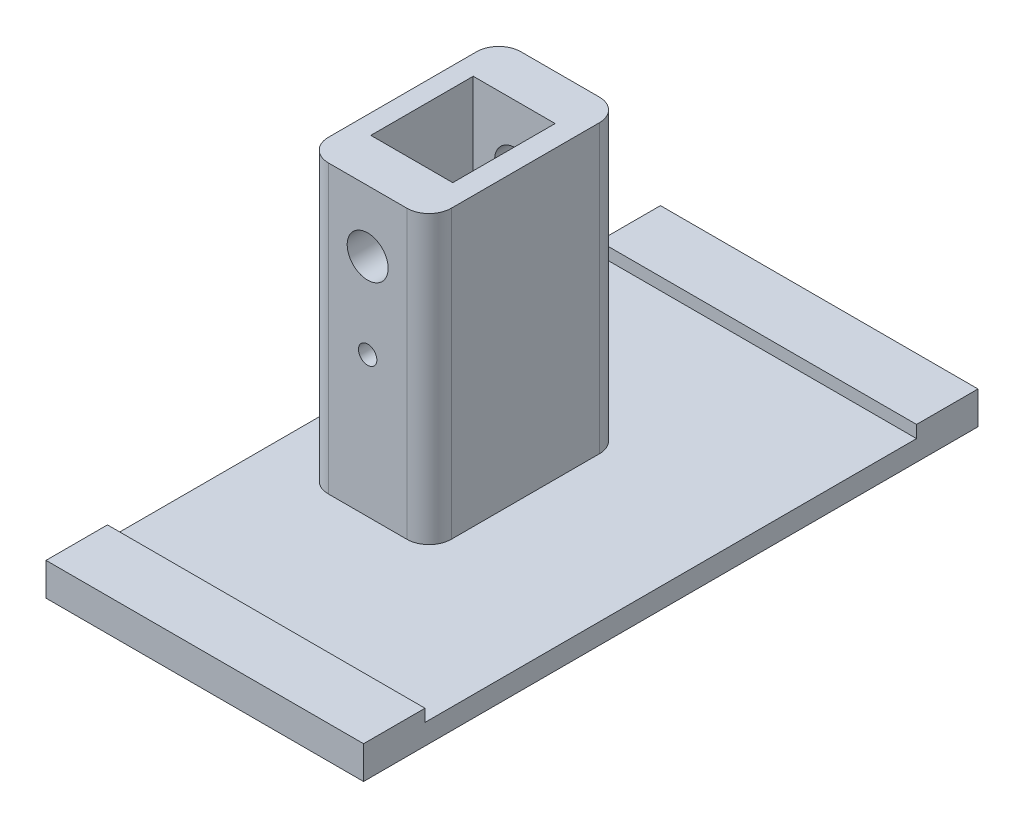
SolidWorks part; units mm, degrees
ref_plane "Front Plane" through (0, 0, 0) normal (0, 0, 1) x (1, 0, 0)
ref_plane "Top Plane" through (0, 0, 0) normal (0, 1, 0) x (1, 0, 0)
ref_plane "Right Plane" through (0, 0, 0) normal (1, 0, 0) x (0, 0, -1)
sketch "Sketch2" plane through (0, 0, 0) normal (0, 1, 0) x (1, 0, 0)
  line L0 (0, 38.1) -> (39.3827, 38.1) construction
  line L1 (0, 0) -> (39.3827, 0)
  line L2 (0, 0) -> (0, 76.2)
  line L3 (0, 76.2) -> (39.3827, 76.2)
  line L4 (39.3827, 0) -> (39.3827, 76.2)
  line L5 (23.9719, 38.1) -> (23.9719, 53.467) construction
  line L6 (23.9719, 38.1) -> (23.9719, 22.733) construction
  line L7 (39.3827, 68.58) -> (0, 68.58)
  line L8 (8.5334, 38.1) -> (8.5334, 31.75)
  line L9 (8.5334, 31.75) -> (18.6934, 31.75)
  line L10 (8.5334, 38.1) -> (8.5334, 44.45)
  line L11 (8.5334, 44.45) -> (18.6934, 44.45)
  line L12 (18.6934, 44.45) -> (18.6934, 31.75)
  line L13 (33.1404, 76.2) -> (33.1404, 68.58) construction
  line L14 (28.6413, 0) -> (28.6413, 7.62) construction
  line L15 (39.3827, 7.62) -> (0, 7.62)
  line L16 (6.1079, 38.1) -> (6.1079, 26.162)
  line L17 (6.1079, 26.162) -> (21.3479, 26.162)
  line L18 (6.1079, 38.1) -> (6.1079, 50.038)
  line L19 (6.1079, 50.038) -> (21.3479, 50.038)
  line L20 (21.3479, 50.038) -> (21.3479, 26.162)
  line L26 (8.5334, 28.702) -> (8.5334, 31.75)
  arc A2 (0, 41.91) -> (0, 34.29) centre (0, 38.1) cw
  dimension "D1" = 5.588
  dimension "D2" = 76.2
  dimension "D3" = 39.3827
  dimension "D4" = 12.7
  dimension "D5" = 15.24
  dimension "D6" = 10.16
extrude "Boss-Extrude2" add sketch "Sketch2" along normal blind 4.064 contours L4 L15 L2 L1 | L7 L4 L3 L2 region at (19.6913, 0, -3.81) region at (19.6913, 0, -72.39)
extrude "Boss-Extrude3" add sketch "Sketch2<3>" along normal blind 2.54 contours L15 L4 L7 L2 | L20 L19 L18 L16 L17 L11 L12 L9 L8 L10 | L12 L11 L10 L8 L9 | L26 L9 | L11 region at (0.7257, 0, -20.955) region at (13.6134, 0, -38.1) region at (6.3911, 0, -44.069)
sketch "Sketch2<3>" plane through (0, 0, 0) normal (0, 1, 0) x (1, 0, 0) same geometry as "Sketch2"
extrude "Boss-Extrude4" add sketch "Sketch2<8>" along normal blind 38.1 contours L20 L19 L18 L16 L17 L26 L8 L10 L12 | L11 | L26 L9 region at (6.3911, 0, -44.069)
sketch "Sketch2<8>" plane through (0, 0, 0) normal (0, 1, 0) x (1, 0, 0) same geometry as "Sketch2"
sketch "Sketch4" plane through (0, 2.54, 0) normal (0, 1, 0) x (1, 0, 0)
  line L0 (18.6934, 44.45) -> (8.5334, 44.45)
  line L1 (8.5334, 44.45) -> (8.5334, 48.26)
  line L2 (8.5334, 48.26) -> (18.6934, 48.26)
  line L3 (18.6934, 48.26) -> (18.6934, 44.45)
  line L4 (8.5334, 31.75) -> (18.6934, 31.75)
  line L5 (18.6934, 31.75) -> (18.6934, 27.94)
  line L6 (18.6934, 27.94) -> (8.5334, 27.94)
  line L7 (8.5334, 27.94) -> (8.5334, 31.75)
extrude "Cut-Extrude2" cut sketch "Sketch4" along normal blind 12.7
sketch "Sketch5" plane through (0, 0, -50.038) normal (0, 0, -1) x (-1, 0, 0)
  line L0 (-21.3479, 30.48) -> (-6.1079, 30.48) construction
  line L1 (-21.3479, 38.1) -> (-21.3479, 2.54) construction
  line L2 (-6.1079, 38.1) -> (-6.1079, 2.54) construction
  line L3 (-13.7279, 30.48) -> (-13.7279, 19.939) construction
  line L4 (-21.3479, 38.1) -> (-6.1079, 38.1) construction
  circle A0 centre (-13.7279, 30.48) radius 2.54
  circle A1 centre (-13.7279, 19.939) radius 1.143
  dimension "D1" = 7.62
extrude "Cut-Extrude3" cut sketch "Sketch5" against normal up to surface (23.876 mm away) up to face at (13.7279, 20.32, -26.162)
sketch "Sketch6" plane through (0, 38.1, 0) normal (0, 1, 0) x (1, 0, 0)
  line L0 (18.5962, 26.162) -> (18.5962, 28.9137) construction
  line L1 (6.1079, 26.162) -> (21.3479, 26.162) construction
  line L2 (18.5962, 28.9137) -> (21.3479, 28.9137) construction
  line L3 (21.3479, 50.038) -> (21.3479, 26.162) construction
  line L4 (21.3479, 28.9137) -> (21.3479, 26.162)
  line L5 (21.3479, 26.162) -> (18.5962, 26.162)
  line L6 (6.1079, 28.9137) -> (8.8595, 28.9137) construction
  line L7 (6.1079, 26.162) -> (6.1079, 50.038) construction
  line L8 (8.8595, 28.9137) -> (8.8595, 26.162) construction
  line L9 (8.8595, 50.038) -> (8.8595, 47.2863) construction
  line L10 (18.5962, 50.038) -> (18.5962, 47.2863) construction
  line L11 (6.1079, 50.038) -> (21.3479, 50.038) construction
  line L12 (18.5962, 47.2863) -> (21.3479, 47.2863) construction
  line L13 (8.8595, 47.2863) -> (6.1079, 47.2863) construction
  line L14 (8.8595, 50.038) -> (6.1079, 50.038)
  line L15 (6.1079, 50.038) -> (6.1079, 47.2863)
  line L16 (6.1079, 28.9137) -> (6.1079, 26.162)
  line L17 (6.1079, 26.162) -> (8.8595, 26.162)
  line L18 (18.5962, 50.038) -> (21.3479, 50.038)
  line L19 (21.3479, 50.038) -> (21.3479, 47.2863)
  arc A0 (21.3479, 28.9137) -> (18.5962, 26.162) centre (18.5962, 28.9137) cw
  arc A1 (8.8595, 50.038) -> (6.1079, 47.2863) centre (8.8595, 47.2863) ccw
  arc A2 (8.8595, 26.162) -> (6.1079, 28.9137) centre (8.8595, 28.9137) cw
  arc A3 (18.5962, 50.038) -> (21.3479, 47.2863) centre (18.5962, 47.2863) cw
  line M5 (21.3479, 26.162) -> (21.3479, 50.038)
  line M6 (21.3479, 50.038) -> (6.1079, 50.038)
  line M7 (6.1079, 50.038) -> (6.1079, 26.162)
  line M8 (6.1079, 26.162) -> (21.3479, 26.162)
extrude "Cut-Extrude5" cut sketch "Sketch6" against normal up to surface (35.56 mm away) contours A1 M6 M7 | A3 M6 M5 | A2 M8 M7 | A0 M5 M8 region at (20.7332, 38.1, -26.7766) region at (20.7332, 38.1, -49.4234) region at (6.7225, 38.1, -26.7766) region at (6.7225, 38.1, -49.4234) up to face at (13.7279, 2.54, -38.1)
